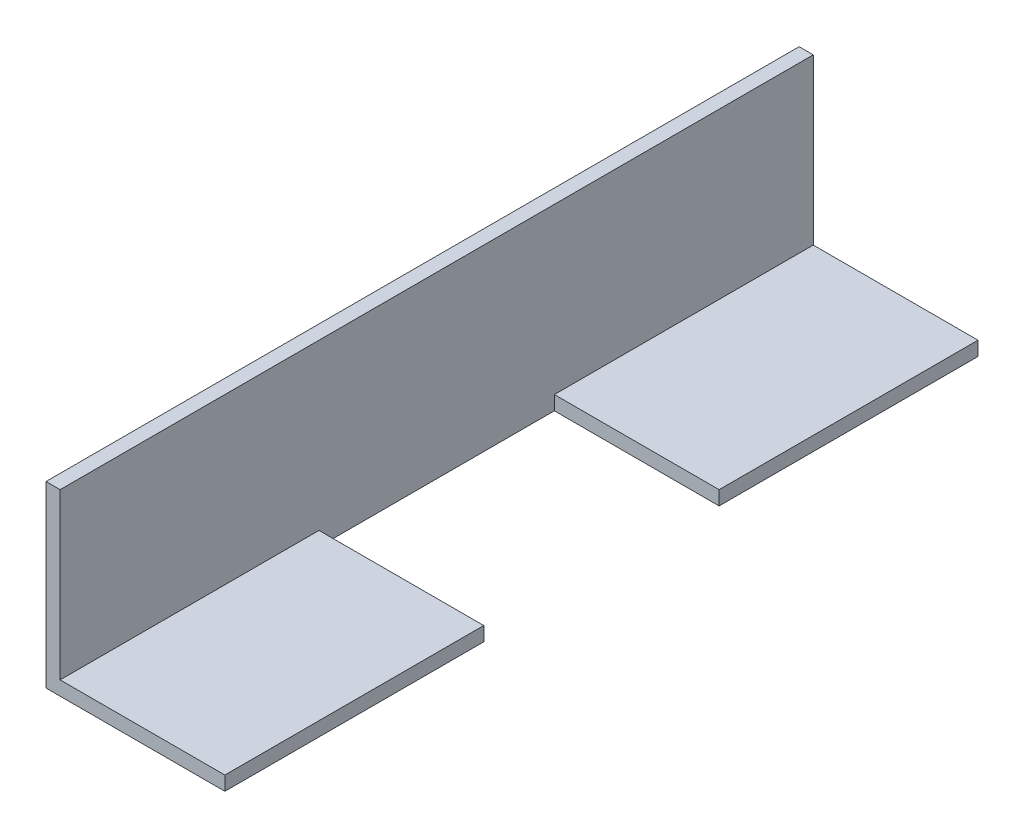
SolidWorks part; units mm, degrees
ref_plane "Alzado" through (0, 0, 0) normal (0, 0, 1) x (1, 0, 0)
ref_plane "Planta" through (0, 0, 0) normal (0, 1, 0) x (1, 0, 0)
ref_plane "Vista lateral" through (0, 0, 0) normal (1, 0, 0) x (0, 0, -1)
sketch "Croquis1" plane through (0, 0, 0) normal (0, 0, 1) x (1, 0, 0)
  line L0 (0, 0) -> (0, 38)
  line L1 (0, 0) -> (38, 0)
  line L2 (3, 3) -> (38, 3)
  line L3 (3, 3) -> (3, 38)
  line L4 (0, 38) -> (3, 38)
  line L5 (38, 3) -> (38, 0)
  dimension "D1" = 38
  dimension "D2" = 3
extrude "Saliente-Extruir1" add sketch "Croquis1" along normal blind 80 and the other way blind 80
sketch "Croquis2" plane through (0, 3, 0) normal (0, 1, 0) x (1, 0, 0)
  line L0 (3, 0) -> (38, 0) construction
  line L1 (3, 80) -> (3, -80) construction
  line L2 (38, 80) -> (38, -80) construction
  line L3 (3, 25) -> (3, -25)
  line L4 (3, -25) -> (38, -25)
  line L5 (38, -25) -> (38, 25)
  line L6 (3, 25) -> (38, 25)
  dimension "D1" = 25
extrude "Cortar-Extruir1" cut sketch "Croquis2" against normal up to surface (3 mm away) up to face at (19, 0, 0)
